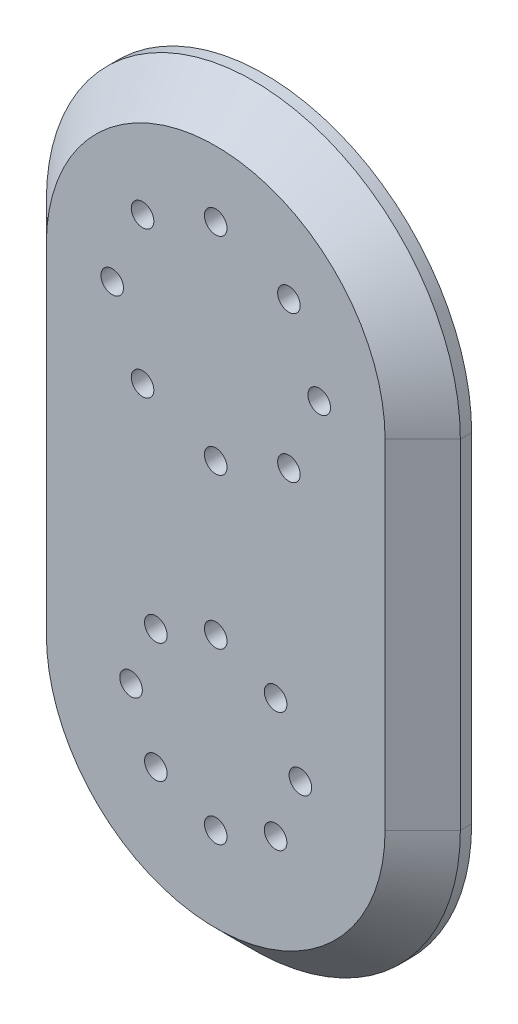
SolidWorks part; units mm, degrees
ref_plane "前视基准面" through (0, 0, 0) normal (0, 0, 1) x (1, 0, 0)
ref_plane "上视基准面" through (0, 0, 0) normal (0, 1, 0) x (1, 0, 0)
ref_plane "右视基准面" through (0, 0, 0) normal (1, 0, 0) x (0, 0, -1)
sketch "草图1" plane through (0, 0, 0) normal (0, 0, 1) x (1, 0, 0)
  line L0 (0, -45) -> (0, 45) construction
  line L1 (-55, -45) -> (-55, 45)
  line L2 (55, -45) -> (55, 45)
  arc A0 (-55, -45) -> (55, -45) centre (0, -45) ccw
  arc A1 (55, 45) -> (-55, 45) centre (0, 45) ccw
  point P3 (0, 0)
  point P8 (0, 0)
  dimension "D1" = 110
  dimension "D2" = 90
extrude "凸台-拉伸1" add sketch "草图1" along normal blind 13
chamfer "倒角1" distance 10 angle 45 4 edges at (0, -100, 13) (55, 0, 13) (-55, 0, 13) (0, 100, 13)
sketch "草图2" plane through (0, 0, 0) normal (0, 0, -1) x (-1, 0, 0)
  line L0 (0, -45) -> (0, 45) construction
  line L1 (-31, -45) -> (-31, -15)
  line L2 (-21, -5) -> (21, -5)
  line L3 (31, -15) -> (31, -45)
  circle A0 centre (0, 45) radius 23.5
  arc A1 (-31, -45) -> (31, -45) centre (0, -45) ccw
  arc A2 (21, -5) -> (31, -15) centre (21, -15) cw
  arc A3 (-31, -15) -> (-21, -5) centre (-21, -15) cw
  point P14 (31, -5)
  point P17 (-31, -5)
  point P18 (0, 0)
  dimension "D1" = 47
  dimension "D4" = 10
  dimension "D2" = 71
  dimension "D3" = 62
extrude "切除-拉伸1" cut sketch "草图2" against normal blind 10 contours A0
extrude "切除-拉伸2" cut sketch "草图2<4>" against normal blind 7 contours L3 A1 L1 A3 L2 A2
sketch "草图2<4>" plane through (0, 0, 0) normal (0, 0, -1) x (-1, 0, 0) same geometry as "草图2"
sketch "草图3" plane through (0, 0, 0) normal (0, 0, -1) x (-1, 0, 0)
  circle A0 centre (0, 45) radius 27.5 construction
  circle A1 centre (0, 72.5) radius 3
  circle A2 centre (19.4454, 64.4454) radius 3
  circle A3 centre (27.5, 45) radius 3
  circle A4 centre (19.4454, 25.5546) radius 3
  circle A5 centre (0, 17.5) radius 3
  circle A6 centre (-19.4454, 25.5546) radius 3
  circle A7 centre (-27.5, 45) radius 3
  circle A8 centre (-19.4454, 64.4454) radius 3
  circle A9 centre (0, -45) radius 22.5 construction
  circle A10 centre (0, -22.5) radius 3
  circle A11 centre (15.9099, -29.0901) radius 3
  circle A12 centre (22.5, -45) radius 3
  circle A13 centre (15.9099, -60.9099) radius 3
  circle A14 centre (0, -67.5) radius 3
  circle A15 centre (-15.9099, -60.9099) radius 3
  circle A16 centre (-22.5, -45) radius 3
  circle A17 centre (-15.9099, -29.0901) radius 3
  point P22 (0, 45)
  point P26 (0, 0)
  point P41 (0, -45)
  dimension "D1" = 55
  dimension "D2" = 6
  dimension "D4" = 45
  dimension "D5" = 6
  dimension "D3" = 8
  dimension "D6" = 8
extrude "切除-拉伸3" cut sketch "草图3" against normal through all
